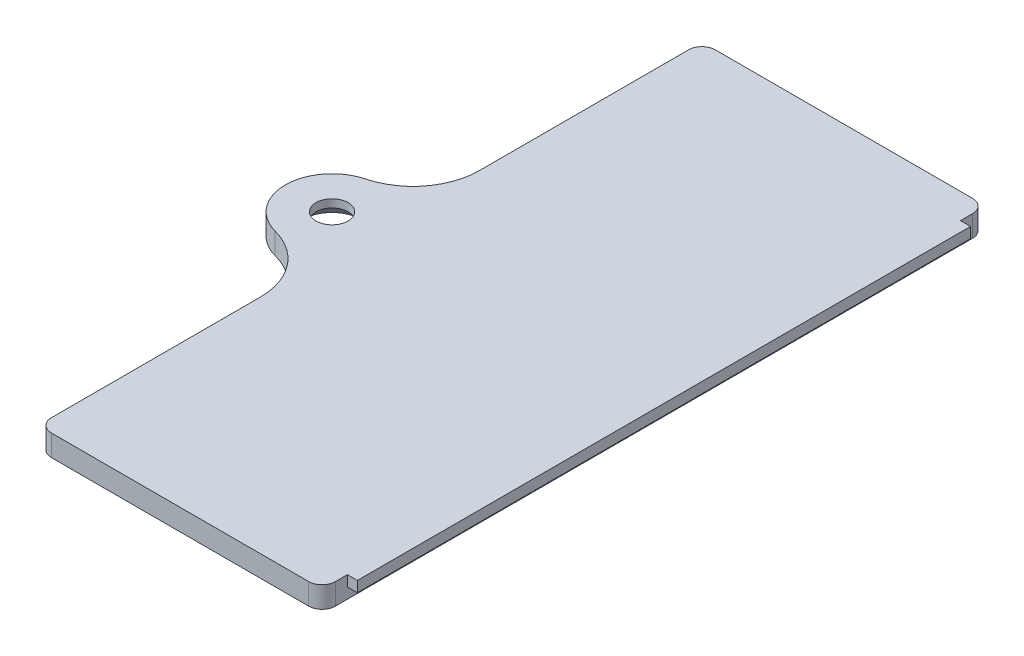
SolidWorks part; units mm, degrees
ref_plane "Front Plane" through (0, 0, 0) normal (0, 0, 1) x (1, 0, 0)
ref_plane "Top Plane" through (0, 0, 0) normal (0, 1, 0) x (1, 0, 0)
ref_plane "Right Plane" through (0, 0, 0) normal (1, 0, 0) x (0, 0, -1)
sketch "Door Plate 1.6 + screw ear (R5 / R3.5) Sketch" plane through (0, 0, 0) normal (0, 1, 0) x (1, 0, 0)
  line L0 (9.35, 15.1) -> (30.65, 15.1)
  line L1 (30.65, 15.1) -> (30.65, 64.9)
  line L2 (30.65, 64.9) -> (9.35, 64.9)
  line L3 (9.35, 64.9) -> (9.35, 48.2236)
  line L4 (9.35, 31.7764) -> (9.35, 15.1)
  arc A0 (9.35, 31.7764) -> (5.6147, 36.6138) centre (4.35, 31.7764) ccw
  arc A1 (5.6147, 36.6138) -> (5.6147, 43.3862) centre (6.5, 40) cw
  arc A2 (5.6147, 43.3862) -> (9.35, 48.2236) centre (4.35, 48.2236) ccw
extrude "Door Plate 1.6 + screw ear (R5 / R3.5)" add sketch "Door Plate 1.6 + screw ear (R5 / R3.5) Sketch" along normal blind 1.6
ref_plane "Hook Flange Plane y0.8" through (0, 0.8, 0) normal (0, 1, 0) x (1, 0, 0)
sketch "Hook Flange 0.75 x 0.8 (inner-face plane) Sketch" plane through (0, 0.8, 0) normal (0, 1, 0) x (1, 0, 0)
  line L0 (30.5, 17) -> (31.4, 17)
  line L1 (31.4, 17) -> (31.4, 63)
  line L2 (31.4, 63) -> (30.5, 63)
  line L3 (30.5, 63) -> (30.5, 17)
extrude "Hook Flange 0.75 x 0.8 (inner-face plane)" add sketch "Hook Flange 0.75 x 0.8 (inner-face plane) Sketch" along normal blind 0.8
sketch "Screw Hole 2.4 (free) Sketch" plane through (0, 0, 0) normal (0, 1, 0) x (1, 0, 0)
  circle A0 centre (6.5, 40) radius 1.2
extrude "Screw Hole 2.4 (free)" cut sketch "Screw Hole 2.4 (free) Sketch" along normal through all
chamfer "Screw CSK 90deg (M2)" distance 1 angle 45 1 edges at (6.5, 0, -38.8)
fillet "Door Corners R1 (print)" radius 1 4 edges at (9.35, 0.8, -64.9) (30.65, 0.8, -64.9) (30.65, 0.8, -15.1) (9.35, 0.8, -15.1)
